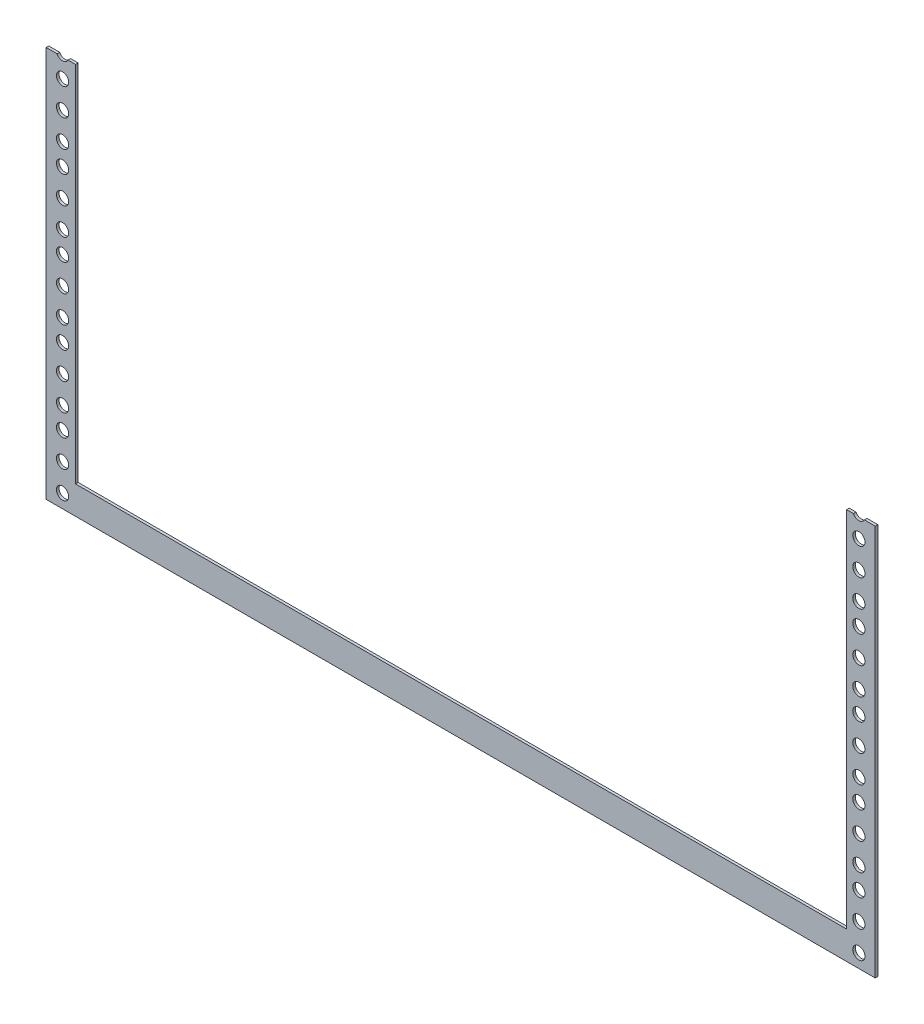
SolidWorks part; units mm, degrees
ref_plane "Front Plane" through (0, 0, 0) normal (0, 0, 1) x (1, 0, 0)
ref_plane "Top Plane" through (0, 0, 0) normal (0, 1, 0) x (1, 0, 0)
ref_plane "Right Plane" through (0, 0, 0) normal (1, 0, 0) x (0, 0, -1)
sketch "Sketch1" plane through (0, 0, 0) normal (0, 0, 1) x (1, 0, 0)
  line L0 (305.5937, 5.842) -> (305.5937, 83.058) construction
  line L1 (305.5937, 5.842) -> (305.5937, 83.058) construction
  line L2 (-305.5937, 5.842) -> (-305.5937, 83.058) construction
  line L3 (-305.5937, 5.842) -> (-305.5937, 83.058) construction
  line L4 (-305.5937, 88.9) -> (-302.4187, 88.9) construction
  line L5 (305.5937, 2181.225) -> (305.5937, 88.9) construction
  line L6 (-242.0938, 2114.55) -> (-242.0938, 155.575)
  line L7 (-261.1438, 2181.225) -> (-261.1438, 131.0257) construction
  line L8 (-305.5937, 2181.225) -> (-305.5937, 88.9) construction
  line L9 (-224.9728, 2114.5499) -> (-225.425, 155.575) construction
  line L10 (242.0938, 155.575) -> (242.0938, 2114.55)
  line L11 (261.1438, 131.0257) -> (261.1438, 2181.225) construction
  line L12 (225.425, 155.575) -> (225.425, 2114.55) construction
  line L13 (-242.0938, 155.575) -> (242.0938, 155.575)
  line L14 (-261.1438, 133.35) -> (261.1438, 133.35) construction
  line L15 (305.5937, 2181.225) -> (-305.5937, 2181.225) construction
  line L16 (242.0938, 2114.55) -> (-242.0938, 2114.55)
  line L17 (261.1438, 2136.775) -> (-261.1438, 2136.775) construction
  line L18 (-305.5937, 88.9) -> (-302.4187, 88.9) construction
  line L19 (270.6688, 38.9507) -> (270.6688, 49.9493) construction
  line L20 (270.6688, 38.9507) -> (270.6688, 49.9493) construction
  line L21 (270.6688, 108.8007) -> (270.6688, 119.7993) construction
  line L22 (289.7188, 38.9507) -> (289.7188, 49.9493) construction
  line L23 (289.7188, 38.9507) -> (289.7188, 49.9493) construction
  line L24 (289.7188, 108.8007) -> (289.7188, 119.7993) construction
  line L25 (-302.4187, 177.8) -> (-264.3187, 177.8) construction
  line L26 (-299.7517, 0) -> (299.7517, 0) construction
  line L27 (-302.4187, 177.8) -> (-264.3187, 177.8) construction
  line L28 (-289.7187, 38.9507) -> (-289.7187, 49.9493) construction
  line L29 (-289.7187, 38.9507) -> (-289.7187, 49.9493) construction
  line L30 (270.6688, 157.8993) -> (270.6688, 146.9007) construction
  line L31 (270.6688, 146.9007) -> (280.1938, 141.4015) construction
  line L32 (280.1938, 141.4015) -> (289.7188, 146.9007) construction
  line L33 (289.7188, 146.9007) -> (289.7188, 157.8993) construction
  line L34 (289.7188, 157.8993) -> (280.1938, 163.3985) construction
  line L35 (280.1938, 163.3985) -> (270.6688, 157.8993) construction
  line L36 (-289.7187, 108.8007) -> (-289.7187, 119.7993) construction
  line L37 (270.6688, 38.9507) -> (280.1938, 33.4515) construction
  line L38 (280.1938, 33.4515) -> (289.7188, 38.9507) construction
  line L39 (-270.6687, 38.9507) -> (-270.6687, 49.9493) construction
  line L40 (289.7188, 49.9493) -> (280.1938, 55.4485) construction
  line L41 (280.1938, 55.4485) -> (270.6688, 49.9493) construction
  line L42 (-270.6687, 38.9507) -> (-270.6687, 49.9493) construction
  line L43 (270.6688, 108.8007) -> (280.1938, 103.3015) construction
  line L44 (280.1938, 103.3015) -> (289.7188, 108.8007) construction
  line L45 (-270.6687, 108.8007) -> (-270.6687, 119.7993) construction
  line L46 (289.7188, 119.7993) -> (280.1938, 125.2985) construction
  line L47 (280.1938, 125.2985) -> (270.6688, 119.7993) construction
  line L48 (264.3188, 177.8) -> (302.4188, 177.8) construction
  line L49 (-212.7314, 119.7993) -> (-212.7314, 108.8007) construction
  line L50 (-212.7314, 108.8007) -> (-203.2064, 103.3015) construction
  line L51 (-203.2064, 103.3015) -> (-193.6814, 108.8007) construction
  line L52 (-193.6814, 108.8007) -> (-193.6814, 119.7993) construction
  line L53 (-193.6814, 119.7993) -> (-203.2064, 125.2985) construction
  line L54 (-203.2064, 125.2985) -> (-212.7314, 119.7993) construction
  line L55 (-9.525, 38.9507) -> (-9.525, 49.9493) construction
  line L56 (-289.7187, 108.8007) -> (-280.1937, 103.3015) construction
  line L57 (-280.1937, 103.3015) -> (-270.6687, 108.8007) construction
  line L58 (-9.525, 38.9507) -> (-9.525, 49.9493) construction
  line L59 (-270.6687, 119.7993) -> (-280.1937, 125.2985) construction
  line L60 (-280.1937, 125.2985) -> (-289.7187, 119.7993) construction
  line L61 (-9.525, 119.7993) -> (-9.525, 108.8007) construction
  line L62 (-9.525, 108.8007) -> (0, 103.3015) construction
  line L63 (0, 103.3015) -> (9.525, 108.8007) construction
  line L64 (9.525, 108.8007) -> (9.525, 119.7993) construction
  line L65 (9.525, 119.7993) -> (0, 125.2985) construction
  line L66 (0, 125.2985) -> (-9.525, 119.7993) construction
  line L67 (193.675, 119.7993) -> (193.675, 108.8007) construction
  line L68 (193.675, 108.8007) -> (203.2, 103.3015) construction
  line L69 (203.2, 103.3015) -> (212.725, 108.8007) construction
  line L70 (212.725, 108.8007) -> (212.725, 119.7993) construction
  line L71 (212.725, 119.7993) -> (203.2, 125.2985) construction
  line L72 (203.2, 125.2985) -> (193.675, 119.7993) construction
  line L73 (9.525, 38.9507) -> (9.525, 49.9493) construction
  line L74 (-289.7187, 38.9507) -> (-280.1937, 33.4515) construction
  line L75 (-280.1937, 33.4515) -> (-270.6687, 38.9507) construction
  line L76 (9.525, 38.9507) -> (9.525, 49.9493) construction
  line L77 (-270.6687, 49.9493) -> (-280.1937, 55.4485) construction
  line L78 (-280.1937, 55.4485) -> (-289.7187, 49.9493) construction
  line L80 (-289.7187, 157.8993) -> (-289.7187, 146.9007) construction
  line L81 (-289.7187, 146.9007) -> (-280.1937, 141.4015) construction
  line L82 (-280.1937, 141.4015) -> (-270.6687, 146.9007) construction
  line L83 (-270.6687, 146.9007) -> (-270.6687, 157.8993) construction
  line L84 (-270.6687, 157.8993) -> (-280.1937, 163.3985) construction
  line L85 (-280.1937, 163.3985) -> (-289.7187, 157.8993) construction
  line L86 (-264.3187, 177.8) -> (-264.3187, 136.525) construction
  line L87 (-257.9687, 130.175) -> (257.9688, 130.175) construction
  line L88 (302.4188, 177.8) -> (302.4188, 1.524) construction
  line L89 (-302.4187, 177.8) -> (-302.4187, 1.524) construction
  line L90 (-302.4187, 1.524) -> (302.4188, 1.524) construction
  line L91 (264.3188, 177.8) -> (264.3188, 136.525) construction
  line L92 (-224.9775, 2094.0964) -> (225.425, 2094.0964)
  line L93 (-9.525, 38.9507) -> (0, 33.4515) construction
  line L94 (0, 33.4515) -> (9.525, 38.9507) construction
  line L95 (-224.9775, 2094.0964) -> (-224.9775, 171.982)
  line L96 (9.525, 49.9493) -> (0, 55.4485) construction
  line L97 (0, 55.4485) -> (-9.525, 49.9493) construction
  line L98 (302.4188, 88.9) -> (305.5937, 88.9) construction
  line L99 (-224.9775, 171.982) -> (225.425, 171.982)
  line L100 (225.425, 2094.0964) -> (225.425, 171.982)
  circle A0 centre (-232.5687, 284.1625) radius 3.5719
  circle A1 centre (-232.5687, 239.7125) radius 3.5719
  circle A2 centre (-232.5687, 252.4125) radius 3.5719
  circle A3 centre (-232.5687, 268.2875) radius 3.5719
  circle A4 centre (-232.5687, 207.9625) radius 3.5719
  circle A5 centre (-232.5687, 195.2625) radius 3.5719
  circle A6 centre (-232.5687, 179.3875) radius 3.5719
  circle A7 centre (-232.5687, 163.5125) radius 3.5719
  circle A8 centre (-232.5687, 223.8375) radius 3.5719
  circle A9 centre (-232.5687, 417.5125) radius 3.5719
  circle A10 centre (-232.5687, 401.6375) radius 3.5719
  circle A11 centre (-232.5687, 373.0625) radius 3.5719
  circle A12 centre (-232.5687, 385.7625) radius 3.5719
  circle A13 centre (-232.5687, 312.7375) radius 3.5719
  circle A14 centre (-232.5687, 296.8625) radius 3.5719
  circle A15 centre (-232.5687, 328.6125) radius 3.5719
  circle A16 centre (-232.5687, 341.3125) radius 3.5719
  circle A17 centre (-232.5687, 357.1875) radius 3.5719
  circle A18 centre (-232.5687, 506.4125) radius 3.5719
  circle A19 centre (-232.5687, 534.9875) radius 3.5719
  circle A20 centre (-232.5687, 519.1125) radius 3.5719
  circle A21 centre (-232.5687, 446.0875) radius 3.5719
  circle A22 centre (-232.5687, 461.9625) radius 3.5719
  circle A23 centre (-232.5687, 430.2125) radius 3.5719
  circle A24 centre (-232.5687, 474.6625) radius 3.5719
  circle A25 centre (-232.5687, 490.5375) radius 3.5719
  circle A26 centre (232.5687, 284.1625) radius 3.5719
  circle A27 centre (232.5687, 239.7125) radius 3.5719
  circle A28 centre (232.5687, 252.4125) radius 3.5719
  circle A29 centre (232.5687, 268.2875) radius 3.5719
  circle A30 centre (232.5687, 207.9625) radius 3.5719
  circle A31 centre (232.5687, 179.3875) radius 3.5719
  circle A32 centre (232.5687, 195.2625) radius 3.5719
  circle A33 centre (232.5687, 163.5125) radius 3.5719
  circle A34 centre (232.5687, 223.8375) radius 3.5719
  circle A35 centre (232.5687, 417.5125) radius 3.5719
  circle A36 centre (232.5687, 401.6375) radius 3.5719
  circle A37 centre (232.5687, 373.0625) radius 3.5719
  circle A38 centre (232.5687, 385.7625) radius 3.5719
  circle A39 centre (232.5687, 312.7375) radius 3.5719
  circle A40 centre (232.5687, 296.8625) radius 3.5719
  circle A41 centre (232.5687, 328.6125) radius 3.5719
  circle A42 centre (232.5687, 357.1875) radius 3.5719
  circle A43 centre (232.5687, 341.3125) radius 3.5719
  circle A44 centre (232.5687, 506.4125) radius 3.5719
  circle A45 centre (232.5687, 534.9875) radius 3.5719
  circle A46 centre (232.5687, 519.1125) radius 3.5719
  circle A47 centre (232.5687, 461.9625) radius 3.5719
  circle A48 centre (232.5687, 446.0875) radius 3.5719
  circle A49 centre (232.5687, 430.2125) radius 3.5719
  circle A50 centre (232.5687, 474.6625) radius 3.5719
  circle A51 centre (232.5687, 490.5375) radius 3.5719
  circle A52 centre (-232.5687, 801.6875) radius 3.5719
  circle A53 centre (-232.5687, 639.7625) radius 3.5719
  circle A54 centre (-232.5687, 652.4625) radius 3.5719
  circle A55 centre (-232.5687, 668.3375) radius 3.5719
  circle A56 centre (-232.5687, 639.7625) radius 3.5719
  circle A57 centre (-232.5687, 668.3375) radius 3.5719
  circle A58 centre (-232.5687, 652.4625) radius 3.5719
  circle A59 centre (-232.5687, 550.8625) radius 3.5719
  circle A60 centre (-232.5687, 579.4375) radius 3.5719
  circle A61 centre (-232.5687, 595.3125) radius 3.5719
  circle A62 centre (-232.5687, 563.5625) radius 3.5719
  circle A63 centre (-232.5687, 608.0125) radius 3.5719
  circle A64 centre (-232.5687, 623.8875) radius 3.5719
  circle A65 centre (-232.5687, 623.8875) radius 3.5719
  circle A66 centre (-232.5687, 757.2375) radius 3.5719
  circle A67 centre (-232.5687, 773.1125) radius 3.5719
  circle A68 centre (-232.5687, 785.8125) radius 3.5719
  circle A69 centre (-232.5687, 757.2375) radius 3.5719
  circle A70 centre (-232.5687, 773.1125) radius 3.5719
  circle A71 centre (-232.5687, 712.7875) radius 3.5719
  circle A72 centre (-232.5687, 684.2125) radius 3.5719
  circle A73 centre (-232.5687, 696.9125) radius 3.5719
  circle A74 centre (-232.5687, 728.6625) radius 3.5719
  circle A75 centre (-232.5687, 741.3625) radius 3.5719
  circle A76 centre (-232.5687, 684.2125) radius 3.5719
  circle A77 centre (-232.5687, 712.7875) radius 3.5719
  circle A78 centre (-232.5687, 728.6625) radius 3.5719
  circle A79 centre (-232.5687, 696.9125) radius 3.5719
  circle A80 centre (-232.5687, 741.3625) radius 3.5719
  circle A81 centre (-232.5687, 935.0375) radius 3.5719
  circle A82 centre (-232.5687, 906.4625) radius 3.5719
  circle A83 centre (-232.5687, 919.1625) radius 3.5719
  circle A84 centre (-232.5687, 890.5875) radius 3.5719
  circle A85 centre (-232.5687, 830.2625) radius 3.5719
  circle A86 centre (-232.5687, 817.5625) radius 3.5719
  circle A87 centre (-232.5687, 846.1375) radius 3.5719
  circle A88 centre (-232.5687, 862.0125) radius 3.5719
  circle A89 centre (-232.5687, 874.7125) radius 3.5719
  circle A90 centre (-232.5687, 1052.5125) radius 3.5719
  circle A91 centre (-232.5687, 1023.9375) radius 3.5719
  circle A92 centre (-232.5687, 1039.8125) radius 3.5719
  circle A93 centre (-232.5687, 950.9125) radius 3.5719
  circle A94 centre (-232.5687, 963.6125) radius 3.5719
  circle A95 centre (-232.5687, 979.4875) radius 3.5719
  circle A96 centre (-232.5687, 995.3625) radius 3.5719
  circle A97 centre (-232.5687, 1008.0625) radius 3.5719
  circle A98 centre (232.5687, 801.6875) radius 3.5719
  circle A99 centre (232.5687, 639.7625) radius 3.5719
  circle A100 centre (232.5687, 652.4625) radius 3.5719
  circle A101 centre (232.5687, 668.3375) radius 3.5719
  circle A102 centre (232.5687, 639.7625) radius 3.5719
  circle A103 centre (232.5687, 668.3375) radius 3.5719
  circle A104 centre (232.5687, 652.4625) radius 3.5719
  circle A105 centre (232.5687, 550.8625) radius 3.5719
  circle A106 centre (232.5687, 595.3125) radius 3.5719
  circle A107 centre (232.5687, 579.4375) radius 3.5719
  circle A108 centre (232.5687, 563.5625) radius 3.5719
  circle A109 centre (232.5687, 608.0125) radius 3.5719
  circle A110 centre (232.5687, 623.8875) radius 3.5719
  circle A111 centre (232.5687, 623.8875) radius 3.5719
  circle A112 centre (232.5687, 773.1125) radius 3.5719
  circle A113 centre (232.5687, 757.2375) radius 3.5719
  circle A114 centre (232.5687, 785.8125) radius 3.5719
  circle A115 centre (232.5687, 773.1125) radius 3.5719
  circle A116 centre (232.5687, 757.2375) radius 3.5719
  circle A117 centre (232.5687, 712.7875) radius 3.5719
  circle A118 centre (232.5687, 684.2125) radius 3.5719
  circle A119 centre (232.5687, 696.9125) radius 3.5719
  circle A120 centre (232.5687, 728.6625) radius 3.5719
  circle A121 centre (232.5687, 741.3625) radius 3.5719
  circle A122 centre (232.5687, 684.2125) radius 3.5719
  circle A123 centre (232.5687, 728.6625) radius 3.5719
  circle A124 centre (232.5687, 712.7875) radius 3.5719
  circle A125 centre (232.5687, 696.9125) radius 3.5719
  circle A126 centre (232.5687, 741.3625) radius 3.5719
  circle A127 centre (232.5687, 935.0375) radius 3.5719
  circle A128 centre (232.5687, 906.4625) radius 3.5719
  circle A129 centre (232.5687, 919.1625) radius 3.5719
  circle A130 centre (232.5687, 890.5875) radius 3.5719
  circle A131 centre (232.5687, 830.2625) radius 3.5719
  circle A132 centre (232.5687, 817.5625) radius 3.5719
  circle A133 centre (232.5687, 862.0125) radius 3.5719
  circle A134 centre (232.5687, 846.1375) radius 3.5719
  circle A135 centre (232.5687, 874.7125) radius 3.5719
  circle A136 centre (232.5687, 1052.5125) radius 3.5719
  circle A137 centre (232.5687, 1039.8125) radius 3.5719
  circle A138 centre (232.5687, 1023.9375) radius 3.5719
  circle A139 centre (232.5687, 950.9125) radius 3.5719
  circle A140 centre (232.5687, 995.3625) radius 3.5719
  circle A141 centre (232.5687, 979.4875) radius 3.5719
  circle A142 centre (232.5687, 963.6125) radius 3.5719
  circle A143 centre (232.5687, 1008.0625) radius 3.5719
  circle A144 centre (-232.5687, 1319.2125) radius 3.5719
  circle A145 centre (-232.5687, 1157.2875) radius 3.5719
  circle A146 centre (-232.5687, 1173.1625) radius 3.5719
  circle A147 centre (-232.5687, 1185.8625) radius 3.5719
  circle A148 centre (-232.5687, 1128.7125) radius 3.5719
  circle A149 centre (-232.5687, 1096.9625) radius 3.5719
  circle A150 centre (-232.5687, 1068.3875) radius 3.5719
  circle A151 centre (-232.5687, 1084.2625) radius 3.5719
  circle A152 centre (-232.5687, 1112.8375) radius 3.5719
  circle A153 centre (-232.5687, 1141.4125) radius 3.5719
  circle A154 centre (-232.5687, 1274.7625) radius 3.5719
  circle A155 centre (-232.5687, 1290.6375) radius 3.5719
  circle A156 centre (-232.5687, 1306.5125) radius 3.5719
  circle A157 centre (-232.5687, 1246.1875) radius 3.5719
  circle A158 centre (-232.5687, 1262.0625) radius 3.5719
  circle A159 centre (-232.5687, 1201.7375) radius 3.5719
  circle A160 centre (-232.5687, 1217.6125) radius 3.5719
  circle A161 centre (-232.5687, 1230.3125) radius 3.5719
  circle A162 centre (-232.5687, 1452.5625) radius 3.5719
  circle A163 centre (-232.5687, 1408.1125) radius 3.5719
  circle A164 centre (-232.5687, 1423.9875) radius 3.5719
  circle A165 centre (-232.5687, 1439.8625) radius 3.5719
  circle A166 centre (-232.5687, 1379.5375) radius 3.5719
  circle A167 centre (-232.5687, 1350.9625) radius 3.5719
  circle A168 centre (-232.5687, 1363.6625) radius 3.5719
  circle A169 centre (-232.5687, 1335.0875) radius 3.5719
  circle A170 centre (-232.5687, 1395.4125) radius 3.5719
  circle A171 centre (-232.5687, 1573.2125) radius 3.5719
  circle A172 centre (-232.5687, 1541.4625) radius 3.5719
  circle A173 centre (-232.5687, 1557.3375) radius 3.5719
  circle A174 centre (-232.5687, 1497.0125) radius 3.5719
  circle A175 centre (-232.5687, 1468.4375) radius 3.5719
  circle A176 centre (-232.5687, 1484.3125) radius 3.5719
  circle A177 centre (-232.5687, 1512.8875) radius 3.5719
  circle A178 centre (-232.5687, 1528.7625) radius 3.5719
  circle A179 centre (232.5687, 1319.2125) radius 3.5719
  circle A180 centre (232.5687, 1157.2875) radius 3.5719
  circle A181 centre (232.5687, 1173.1625) radius 3.5719
  circle A182 centre (232.5687, 1185.8625) radius 3.5719
  circle A183 centre (232.5687, 1128.7125) radius 3.5719
  circle A184 centre (232.5687, 1084.2625) radius 3.5719
  circle A185 centre (232.5687, 1068.3875) radius 3.5719
  circle A186 centre (232.5687, 1096.9625) radius 3.5719
  circle A187 centre (232.5687, 1112.8375) radius 3.5719
  circle A188 centre (232.5687, 1141.4125) radius 3.5719
  circle A189 centre (232.5687, 1274.7625) radius 3.5719
  circle A190 centre (232.5687, 1306.5125) radius 3.5719
  circle A191 centre (232.5687, 1290.6375) radius 3.5719
  circle A192 centre (232.5687, 1262.0625) radius 3.5719
  circle A193 centre (232.5687, 1246.1875) radius 3.5719
  circle A194 centre (232.5687, 1217.6125) radius 3.5719
  circle A195 centre (232.5687, 1201.7375) radius 3.5719
  circle A196 centre (232.5687, 1230.3125) radius 3.5719
  circle A197 centre (232.5687, 1452.5625) radius 3.5719
  circle A198 centre (232.5687, 1439.8625) radius 3.5719
  circle A199 centre (232.5687, 1423.9875) radius 3.5719
  circle A200 centre (232.5687, 1408.1125) radius 3.5719
  circle A201 centre (232.5687, 1379.5375) radius 3.5719
  circle A202 centre (232.5687, 1350.9625) radius 3.5719
  circle A203 centre (232.5687, 1363.6625) radius 3.5719
  circle A204 centre (232.5687, 1335.0875) radius 3.5719
  circle A205 centre (232.5687, 1395.4125) radius 3.5719
  circle A206 centre (232.5687, 1573.2125) radius 3.5719
  circle A207 centre (232.5687, 1541.4625) radius 3.5719
  circle A208 centre (232.5687, 1557.3375) radius 3.5719
  circle A209 centre (232.5687, 1497.0125) radius 3.5719
  circle A210 centre (232.5687, 1484.3125) radius 3.5719
  circle A211 centre (232.5687, 1468.4375) radius 3.5719
  circle A212 centre (232.5687, 1512.8875) radius 3.5719
  circle A213 centre (232.5687, 1528.7625) radius 3.5719
  circle A214 centre (-232.5687, 1839.9125) radius 3.5719
  circle A215 centre (-232.5687, 1706.5625) radius 3.5719
  circle A216 centre (-232.5687, 1662.1125) radius 3.5719
  circle A217 centre (-232.5687, 1690.6875) radius 3.5719
  circle A218 centre (-232.5687, 1674.8125) radius 3.5719
  circle A219 centre (-232.5687, 1601.7875) radius 3.5719
  circle A220 centre (-232.5687, 1585.9125) radius 3.5719
  circle A221 centre (-232.5687, 1617.6625) radius 3.5719
  circle A222 centre (-232.5687, 1646.2375) radius 3.5719
  circle A223 centre (-232.5687, 1630.3625) radius 3.5719
  circle A224 centre (-232.5687, 1795.4625) radius 3.5719
  circle A225 centre (-232.5687, 1808.1625) radius 3.5719
  circle A226 centre (-232.5687, 1824.0375) radius 3.5719
  circle A227 centre (-232.5687, 1779.5875) radius 3.5719
  circle A228 centre (-232.5687, 1751.0125) radius 3.5719
  circle A229 centre (-232.5687, 1719.2625) radius 3.5719
  circle A230 centre (-232.5687, 1735.1375) radius 3.5719
  circle A231 centre (-232.5687, 1763.7125) radius 3.5719
  circle A232 centre (-232.5687, 1928.8125) radius 3.5719
  circle A233 centre (-232.5687, 1941.5125) radius 3.5719
  circle A234 centre (-232.5687, 1957.3875) radius 3.5719
  circle A235 centre (-232.5687, 1897.0625) radius 3.5719
  circle A236 centre (-232.5687, 1868.4875) radius 3.5719
  circle A237 centre (-232.5687, 1884.3625) radius 3.5719
  circle A238 centre (-232.5687, 1852.6125) radius 3.5719
  circle A239 centre (-232.5687, 1912.9375) radius 3.5719
  circle A240 centre (-232.5687, 2090.7375) radius 3.5719
  circle A241 centre (-232.5687, 2062.1625) radius 3.5719
  circle A242 centre (-232.5687, 2074.8625) radius 3.5719
  circle A243 centre (-232.5687, 2001.8375) radius 3.5719
  circle A244 centre (-232.5687, 1973.2625) radius 3.5719
  circle A245 centre (-232.5687, 1985.9625) radius 3.5719
  circle A246 centre (-232.5687, 2017.7125) radius 3.5719
  circle A247 centre (-232.5687, 2030.4125) radius 3.5719
  circle A248 centre (-232.5687, 2046.2875) radius 3.5719
  circle A249 centre (232.5687, 1839.9125) radius 3.5719
  circle A250 centre (232.5687, 1706.5625) radius 3.5719
  circle A251 centre (232.5687, 1662.1125) radius 3.5719
  circle A252 centre (232.5687, 1690.6875) radius 3.5719
  circle A253 centre (232.5687, 1674.8125) radius 3.5719
  circle A254 centre (232.5687, 1601.7875) radius 3.5719
  circle A255 centre (232.5687, 1585.9125) radius 3.5719
  circle A256 centre (232.5687, 1617.6625) radius 3.5719
  circle A257 centre (232.5687, 1646.2375) radius 3.5719
  circle A258 centre (232.5687, 1630.3625) radius 3.5719
  circle A259 centre (232.5687, 1795.4625) radius 3.5719
  circle A260 centre (232.5687, 1824.0375) radius 3.5719
  circle A261 centre (232.5687, 1808.1625) radius 3.5719
  circle A262 centre (232.5687, 1779.5875) radius 3.5719
  circle A263 centre (232.5687, 1751.0125) radius 3.5719
  circle A264 centre (232.5687, 1719.2625) radius 3.5719
  circle A265 centre (232.5687, 1735.1375) radius 3.5719
  circle A266 centre (232.5687, 1763.7125) radius 3.5719
  circle A267 centre (232.5687, 1928.8125) radius 3.5719
  circle A268 centre (232.5687, 1941.5125) radius 3.5719
  circle A269 centre (232.5687, 1957.3875) radius 3.5719
  circle A270 centre (232.5687, 1897.0625) radius 3.5719
  circle A271 centre (232.5687, 1884.3625) radius 3.5719
  circle A272 centre (232.5687, 1868.4875) radius 3.5719
  circle A273 centre (232.5687, 1852.6125) radius 3.5719
  circle A274 centre (232.5687, 1912.9375) radius 3.5719
  circle A275 centre (232.5687, 2090.7375) radius 3.5719
  circle A276 centre (232.5687, 2062.1625) radius 3.5719
  circle A277 centre (232.5687, 2074.8625) radius 3.5719
  circle A278 centre (232.5687, 2001.8375) radius 3.5719
  circle A279 centre (232.5687, 1973.2625) radius 3.5719
  circle A280 centre (232.5687, 1985.9625) radius 3.5719
  circle A281 centre (232.5687, 2017.7125) radius 3.5719
  circle A282 centre (232.5687, 2030.4125) radius 3.5719
  circle A283 centre (232.5687, 2046.2875) radius 3.5719
  circle A284 centre (-232.5687, 2106.6125) radius 3.5719
  circle A285 centre (232.5687, 2106.6125) radius 3.5719
  arc A290 (299.7517, 0) -> (305.5937, 5.842) centre (299.7517, 5.842) ccw construction
  arc A291 (305.5937, 83.058) -> (302.4188, 88.2557) centre (299.7517, 83.058) ccw construction
  arc A292 (-305.5937, 5.842) -> (-299.7517, 0) centre (-299.7517, 5.842) ccw construction
  arc A293 (-302.4187, 88.2557) -> (-305.5937, 83.058) centre (-299.7517, 83.058) ccw construction
  circle A294 centre (280.1938, 152.4) radius 9.525 construction
  circle A295 centre (280.1938, 44.45) radius 9.525 construction
  circle A296 centre (280.1938, 114.3) radius 9.525 construction
  circle A297 centre (-203.2064, 114.3) radius 9.525 construction
  circle A298 centre (-280.1937, 114.3) radius 9.525 construction
  circle A299 centre (0, 114.3) radius 9.525 construction
  circle A300 centre (203.2, 114.3) radius 9.525 construction
  circle A301 centre (-280.1937, 44.45) radius 9.525 construction
  circle A302 centre (-280.1937, 152.4) radius 9.525 construction
  arc A303 (-264.3187, 136.525) -> (-257.9687, 130.175) centre (-257.9687, 136.525) ccw construction
  arc A304 (257.9688, 130.175) -> (264.3188, 136.525) centre (257.9688, 136.525) ccw construction
  circle A305 centre (0, 44.45) radius 9.525 construction
sheet metal parameters "Sheet-Metal1" thickness 1.524 parameters "D1"=1.905
base flange "Base-Flange1" sketch "Sketch1" thickness 1.524 reverse thickness direction yes parameters "D1"=1.905
sketch "Sketch2" plane through (0, 0, 1.524) normal (0, 0, 1) x (1, 0, 0)
  line L0 (242.0938, 155.575) -> (242.0938, 2114.55) construction
  line L1 (-242.0938, 2114.55) -> (242.0938, 2114.55)
  line L2 (-242.0938, 2114.55) -> (-242.0937, 384.175)
  line L3 (-242.0937, 384.175) -> (242.0938, 384.175)
  line L4 (242.0938, 2114.55) -> (242.0938, 384.175)
  line L5 (-242.0938, 155.575) -> (242.0938, 155.575) construction
  dimension "D1" = 228.6
extrude "Extrude1" cut sketch "Sketch2" against normal through all normal cut yes
flat pattern "Flat-Pattern1" [suppressed]
sketch "Bend-Lines1" plane through (0, 0, 0) normal (0, 1, 0) x (-1, 0, 0)
